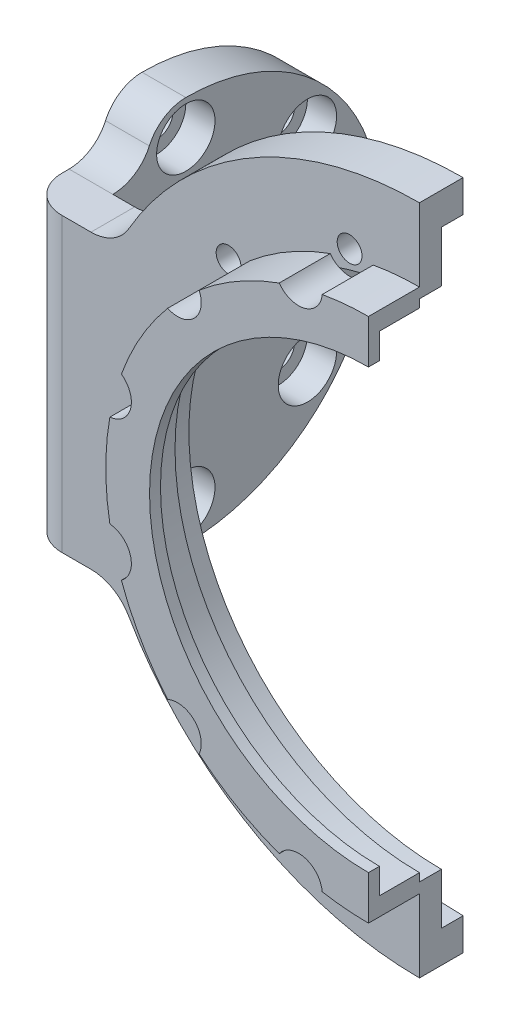
SolidWorks part; units mm, degrees
ref_plane "前视基准面" through (0, 0, 0) normal (0, 0, 1) x (1, 0, 0)
ref_plane "上视基准面" through (0, 0, 0) normal (0, 1, 0) x (1, 0, 0)
ref_plane "右视基准面" through (0, 0, 0) normal (1, 0, 0) x (0, 0, -1)
sketch "草图3" plane through (0, 0, 0) normal (0, 0, 1) x (1, 0, 0)
  circle A0 centre (0, 0) radius 34.6
  circle A1 centre (0, 0) radius 46
extrude "凸台-拉伸2" add sketch "草图3" along normal blind 3
ref_plane "基准面5" through (0, 0, 3) normal (0, 0, 1) x (1, 0, 0)
sketch "草图5" plane through (0, 0, 3) normal (0, 0, 1) x (1, 0, 0)
  circle A0 centre (0, 0) radius 33.5
  circle A1 centre (0, 0) radius 36
extrude "凸台-拉伸3" add sketch "草图5" along normal blind 5.49
sketch "草图2" plane through (0, 0, 0) normal (0, 0, 1) x (1, 0, 0)
  circle A0 centre (0, 0) radius 41.6
  circle A1 centre (0, 0) radius 46
extrude "凸台-拉伸1" add sketch "草图2" against normal blind 2.98
sketch "草图6" plane through (0, 0, 8.49) normal (0, 0, 1) x (1, 0, 0)
  circle A0 centre (0, 0) radius 30
  circle A1 centre (0, 0) radius 36
extrude "凸台-拉伸4" add sketch "草图6" along normal blind 1.5
sketch "草图8" plane through (0, 0, 0) normal (0, 0, 1) x (1, 0, 0)
  line L6 (-50, 20.008) -> (-45.0139, 20.008)
  line L8 (7.1335, 0) -> (-7.1335, 0) construction
  line L10 (-50, 20.008) -> (-50, -20.008)
  line L11 (-50, -20.008) -> (-45.0139, -20.008)
  arc A16 (-45.0139, 20.008) -> (-39.8396, 22.9958) centre (-45.0139, 25.9824) ccw
  arc A17 (-39.8396, 22.9958) -> (-39.8396, -22.9958) centre (0, 0) ccw
  arc A19 (-45.0139, -20.008) -> (-39.8396, -22.9958) centre (-45.0139, -25.9824) cw
extrude "凸台-拉伸5" add sketch "草图8" along normal blind 3 and the other way blind 2.98
hole_wizard "大小mm 暗销孔2" positions "3D草图3" profile "草图12" hole size "Ø1.0" standard "BSI" end condition through all
sketch3d "3D草图3"
  line L2 (0, 0, 0) -> (0, 37, 0)
  line L3 (0, 0, 0) -> (11.5811, 0, 0)
  point P55 (9.5763, 35.7393, 3)
  point P76 (26.163, 26.163, 3)
  point P83 (35.7393, 9.5763, 3)
  point P96 (-35.7393, 9.5763, 3)
  point P97 (-26.163, 26.163, 3)
  point P98 (-9.5763, 35.7393, 3)
  point P99 (35.7393, -9.5763, 3)
  point P100 (26.163, -26.163, 3)
  point P101 (9.5763, -35.7393, 3)
  point P102 (-9.5763, -35.7393, 3)
  point P103 (-26.163, -26.163, 3)
  point P104 (-35.7393, -9.5763, 3)
sketch "草图12" plane through (-35.7393, -9.5763, 3) normal (1, 0, 0) x (0, -1, 0)
  line L0 (0, 0) -> (0, 5.98)
  line L1 (0, 5.98) -> (1.7, 5.98)
  line L2 (1.7, 5.98) -> (1.7, 0)
  line L5 (1.7, 0) -> (0, 0)
  line L11 (0, -6.35) -> (0, 107.95) construction
  dimension "通孔孔直径" = 3.4
  dimension "通孔孔深度" = 5.98
sketch "草图13" plane through (0, 0, 3) normal (0, 0, 1) x (1, 0, 0)
  line L0 (0, 0) -> (0, 10.9464)
  line L1 (0, 0) -> (8.3109, 0)
  circle A0 centre (-35.7393, 9.5763) radius 1.7
  circle A1 centre (-26.163, 26.163) radius 2.2
  circle A2 centre (-9.5763, 35.7393) radius 2.2
  circle A3 centre (-9.5763, -35.7393) radius 2.2
  circle A4 centre (-26.163, -26.163) radius 2.2
  circle A5 centre (-35.7393, -9.5763) radius 1.7
  circle A6 centre (9.5763, -35.7393) radius 2.2
  circle A7 centre (26.163, -26.163) radius 2.2
  circle A8 centre (9.5763, 35.7393) radius 2.2
  circle A9 centre (26.163, 26.163) radius 2.2
  circle A10 centre (35.7393, -9.5763) radius 1.7
  circle A11 centre (35.7393, 9.5763) radius 1.7
extrude "切除-拉伸1" cut sketch "草图13" along normal up to next contours A5 | A4 | A0 | A1 | A2 | A9 | A11 | A10 | A6 | A3 | A8 | A7 region at (-35.7393, 9.5763, 3) region at (-26.163, 26.163, 3) region at (-9.5763, 35.7393, 3) region at (-9.5763, -35.7393, 3) region at (-26.163, -26.163, 3) region at (-35.7393, -9.5763, 3) region at (9.5763, -35.7393, 3) region at (26.163, 26.163, 3) region at (35.7393, -9.5763, 3) region at (35.7393, 9.5763, 3)
sketch "草图25" plane through (0, 0, 3) normal (0, 0, 1) x (1, 0, 0)
  circle A0 centre (-9.5763, 35.7393) radius 3.25
  circle A1 centre (-26.163, 26.163) radius 3.25
  circle A2 centre (-35.7393, 9.5763) radius 3.25
  circle A3 centre (-35.7393, -9.5763) radius 3.25
  circle A4 centre (-26.163, -26.163) radius 3.25
  circle A5 centre (-9.5763, -35.7393) radius 3.25
extrude "切除-拉伸9" cut sketch "草图25" along normal blind 10
ref_plane "基准面6" through (-50, 0, 0) normal (-1, 0, 0) x (0, 0, 1)
sketch "草图26" plane through (-50, 0, 0) normal (-1, 0, 0) x (0, 0, 1)
  line L1 (-2.98, -20.008) -> (3, -20.008)
  line L5 (3, 20.008) -> (3, -20.008) construction
  line L6 (-2.98, 20.008) -> (3, 20.008)
  line L7 (3, 12.2277) -> (3, 23.2096) construction
  line L8 (3, 20.008) -> (3, -20.008)
  line L9 (-2.98, -20.008) -> (3, -20.008)
  arc A8 (-12.98, 26.5) -> (-12.98, -26.5) centre (-12.98, 0) ccw
  arc A9 (-12.98, 26.5) -> (-7.98, 23.254) centre (-12.98, 21.0261) cw
  arc A10 (-2.98, 20.008) -> (-7.98, 23.254) centre (-2.98, 25.4819) cw
  arc A11 (-2.98, -20.008) -> (-7.98, -23.254) centre (-2.98, -25.4819) ccw
  arc A12 (-12.98, -26.5) -> (-7.98, -23.254) centre (-12.98, -21.0261) ccw
extrude "凸台-拉伸7" add sketch "草图26" along normal blind 4 and the other way blind 2 contours A8 A12 A11 L1 L8 L6 A10 A9 region at (-50, 0, -16.9157)
sketch "草图27" plane through (0, 0, 0) normal (0, 0, 1) x (1, 0, 0)
  line L0 (0, 0) -> (0, 46)
  line L1 (0, -46) -> (0, 0)
  arc A0 (-39.8396, -22.9958) -> (-39.8396, 22.9958) centre (0, 0) ccw construction
  arc A1 (0, 46) -> (0, -46) centre (0, 0) cw
extrude "切除-拉伸10" cut sketch "草图27" against normal through all both and the other way through all
hole_wizard "M4 六角凹头盖的柱孔3" positions "3D草图5" profile "草图29" counterbore size "M4" standard "BSI" end condition up to next
sketch3d "3D草图5"
  point P0 (-48, 21.75, -12.98)
  point P4 (-48, 13.9806, -29.6415)
  point P28 (-48, -13.9806, -29.6415)
  point P29 (-48, -21.75, -12.98)
sketch "草图29" plane through (-48, 21.75, -12.98) normal (0, 1, 0) x (0, 0, -1)
  line L0 (0, 0) -> (0, 6)
  line L1 (0, 6) -> (2.25, 6)
  line L3 (2.25, 6) -> (2.25, 4)
  line L4 (2.25, 4) -> (4, 4)
  line L5 (4, 4) -> (4, 0)
  line L7 (4, 0) -> (0, 0)
  line L11 (0, -6.35) -> (0, 107.95) construction
  dimension "通孔孔直径" = 4.5
  dimension "通孔孔深度" = 6
  dimension "柱形沉头孔直径" = 8
  dimension "柱形沉头孔深度" = 4
fillet "圆角1" radius 5 1 edges at (-54, 0, 3)
